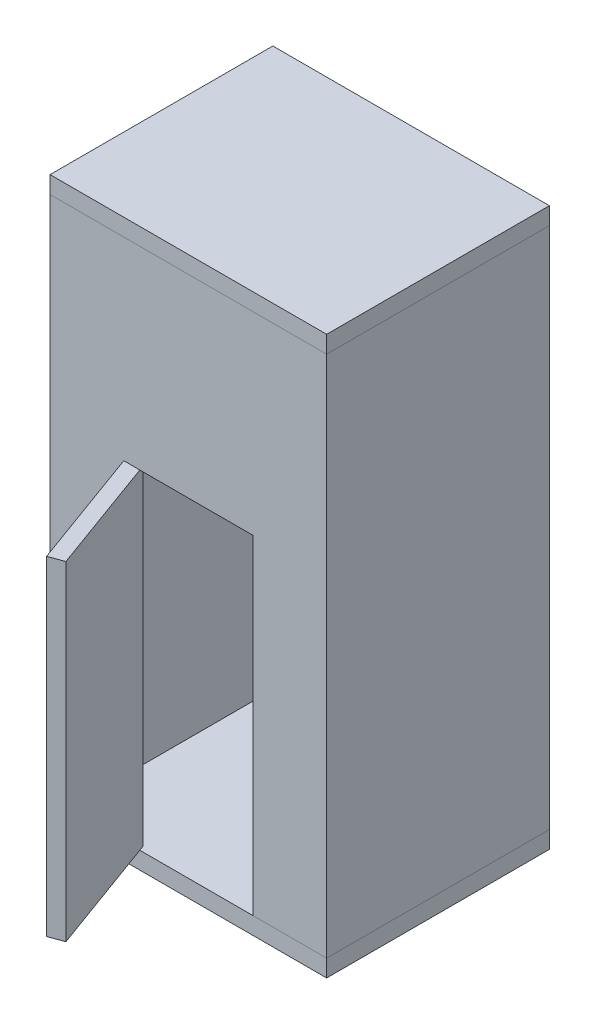
SolidWorks part; units mm, degrees
ref_plane "Front" through (0, 0, 0) normal (0, 0, 1) x (1, 0, 0)
ref_plane "Top" through (0, 0, 0) normal (0, 1, 0) x (1, 0, 0)
ref_plane "Right" through (0, 0, 0) normal (1, 0, 0) x (0, 0, -1)
sketch "Sketch1" plane through (0, 0, 0) normal (0, 1, 0) x (1, 0, 0)
  line L0 (-714.375, 555.625) -> (714.375, 555.625)
  line L1 (-815.975, -657.225) -> (815.975, -657.225)
  line L2 (-815.975, -657.225) -> (-815.975, 657.225)
  line L3 (-815.975, 657.225) -> (815.975, 657.225)
  line L4 (815.975, -657.225) -> (815.975, 657.225)
  line L5 (-815.975, -657.225) -> (815.975, 657.225) construction
  line L6 (-815.975, 657.225) -> (815.975, -657.225) construction
  line L7 (714.375, -555.625) -> (714.375, 555.625)
  line L8 (-714.375, -555.625) -> (714.375, -555.625)
  line L9 (-714.375, -555.625) -> (-714.375, 555.625)
  point P0 (0, 0)
  dimension "D1" = 1314.45
  dimension "D2" = 1631.95
  dimension "D3" = 101.6
extrude "Boss-Extrude1" add sketch "Sketch1" along normal blind 3086.1
sketch "Sketch2" plane through (0, 3086.1, 0) normal (0, 1, 0) x (1, 0, 0)
  line L4 (815.975, -657.225) -> (815.975, 657.225)
  line L5 (815.975, 657.225) -> (-815.975, 657.225)
  line L6 (-815.975, 657.225) -> (-815.975, -657.225)
  line L7 (-815.975, -657.225) -> (815.975, -657.225)
  line L8 (815.975, -657.225) -> (815.975, 657.225)
  line L9 (815.975, 657.225) -> (-815.975, 657.225)
  line L10 (-815.975, 657.225) -> (-815.975, -657.225)
  line L11 (-815.975, -657.225) -> (815.975, -657.225)
  dimension "D1" = 0
extrude "Boss-Extrude2" add sketch "Sketch2" along normal blind 101.6 separate body
sketch "Sketch3" plane through (0, 0, 657.225) normal (0, 0, 1) x (1, 0, 0)
  line L0 (-815.975, 0) -> (815.975, 0) construction
  line L1 (-381, 0) -> (381, 0)
  line L2 (-381, 0) -> (-381, 1943.1)
  line L3 (-381, 1943.1) -> (381, 1943.1)
  line L4 (381, 0) -> (381, 1943.1)
  line L5 (0, 1943.1) -> (0, 0) construction
  dimension "D1" = 1943.1
  dimension "D2" = 762
extrude "Cut-Extrude1" cut sketch "Sketch3" against normal up to next (101.6 mm away)
sketch "Sketch4" plane through (0, 0, 0) normal (0, -1, 0) x (1, 0, 0)
  line L1 (-815.975, -657.225) -> (815.975, -657.225)
  line L2 (-815.975, -657.225) -> (-815.975, 657.225)
  line L3 (-815.975, 657.225) -> (815.975, 657.225)
  line L4 (815.975, -657.225) -> (815.975, 657.225)
  line L5 (-815.975, -657.225) -> (815.975, 657.225) construction
  line L6 (-815.975, 657.225) -> (815.975, -657.225) construction
  point P0 (0, 0)
extrude "Boss-Extrude3" add sketch "Sketch4" along normal blind 101.6 separate body
sketch "Sketch5" plane through (0, 0, -555.625) normal (0, 0, 1) x (1, 0, 0)
  line L4 (-714.375, 0) -> (714.375, 0)
  line L5 (714.375, 0) -> (714.375, 3086.1)
  line L6 (714.375, 3086.1) -> (-714.375, 3086.1)
  line L7 (-714.375, 3086.1) -> (-714.375, 0)
  line L8 (-714.375, 0) -> (714.375, 0)
  line L9 (714.375, 0) -> (714.375, 3086.1)
  line L10 (714.375, 3086.1) -> (-714.375, 3086.1)
  line L11 (-714.375, 3086.1) -> (-714.375, 0)
  dimension "D1" = 0
extrude "Cut-Extrude2" cut sketch "Sketch5" against normal through all
sketch "Sketch6" plane through (0, 1943.1, 0) normal (0, -1, 0) x (1, 0, 0)
  line L0 (-381, 657.225) -> (-120.3807, 1373.2708)
  line L1 (-120.3807, 1373.2708) -> (-36.842, 1342.8652)
  line L2 (-36.842, 1342.8652) -> (-297.4613, 626.8194)
  line L3 (-297.4613, 626.8194) -> (-381, 657.225)
  line L4 (381, 657.225) -> (-381, 657.225) construction
  dimension "D1" = 762
  dimension "D2" = 88.9
  dimension "D3" = 70
extrude "Boss-Extrude4" add sketch "Sketch6" along normal up to surface (1943.1 mm away) separate body up to face at (0, 0, 0)
